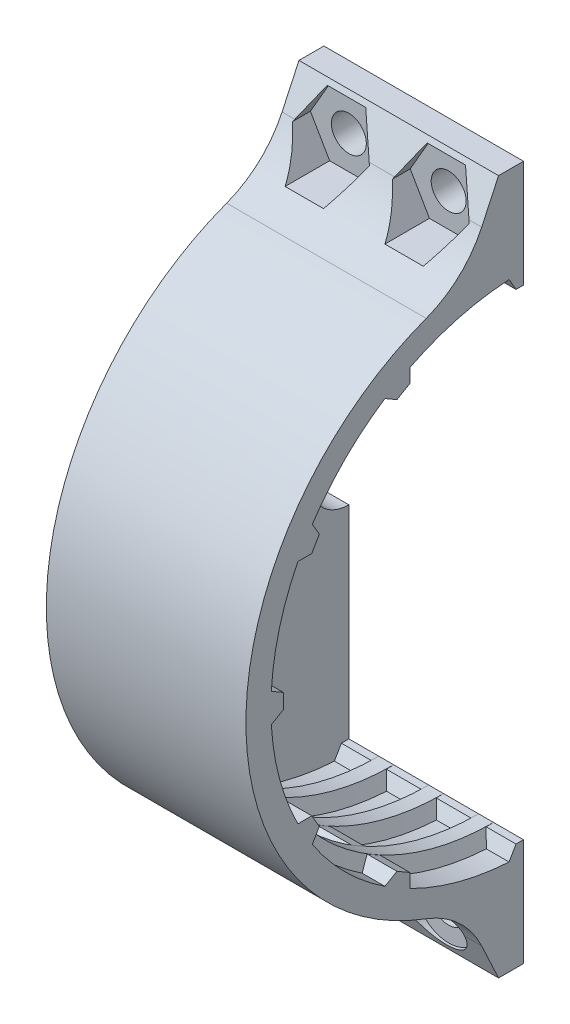
SolidWorks part; units mm, degrees
ref_plane "Front Plane" through (0, 0, 0) normal (0, 0, 1) x (1, 0, 0)
ref_plane "Top Plane" through (0, 0, 0) normal (0, 1, 0) x (1, 0, 0)
ref_plane "Right Plane" through (0, 0, 0) normal (1, 0, 0) x (0, 0, -1)
sketch "Sketch1" plane through (0, 0, 0) normal (0, 1, 0) x (1, 0, 0)
  line L0 (0, 4.7625) -> (0, 35.3219)
  line L1 (0, 35.3219) -> (25.4, 35.3219)
  line L2 (25.4, 35.3219) -> (25.4, 32.1469)
  line L3 (25.4, 32.1469) -> (3.175, 32.1469)
  line L4 (3.175, 32.1469) -> (3.175, 4.7625)
  line L8 (1.5875, 0) -> (24.5079, 0) construction
  line L9 (0, 4.7625) -> (3.175, 4.7625)
  line L15 (13.335, 30.5594) -> (15.24, 30.5594)
  line L16 (15.24, 30.5594) -> (16.1565, 32.1469)
  line L17 (6.985, 30.5594) -> (6.0685, 32.1469)
  line L18 (6.985, 33.7344) -> (8.89, 33.7344)
  line L19 (6.985, 33.7344) -> (6.985, 30.5594)
  line L20 (6.985, 30.5594) -> (8.89, 30.5594)
  line L21 (8.89, 33.7344) -> (8.89, 30.5594)
  line L22 (6.985, 33.7344) -> (8.89, 30.5594) construction
  line L23 (6.985, 30.5594) -> (8.89, 33.7344) construction
  line L28 (13.335, 33.7344) -> (15.24, 30.5594) construction
  line L29 (13.335, 30.5594) -> (12.4185, 32.1469)
  line L30 (8.89, 30.5594) -> (9.8065, 32.1469)
  line L31 (13.335, 33.7344) -> (13.335, 30.5594)
  line L32 (13.335, 30.5594) -> (15.24, 33.7344) construction
  line L33 (13.335, 33.7344) -> (15.24, 33.7344)
  line L34 (15.24, 33.7344) -> (15.24, 30.5594)
  line L35 (19.685, 30.5594) -> (21.59, 30.5594)
  line L36 (21.59, 30.5594) -> (22.5065, 32.1469)
  line L37 (19.685, 33.7344) -> (21.59, 30.5594) construction
  line L38 (19.685, 30.5594) -> (18.7685, 32.1469)
  line L39 (19.685, 33.7344) -> (19.685, 30.5594)
  line L40 (19.685, 30.5594) -> (21.59, 33.7344) construction
  line L41 (19.685, 33.7344) -> (21.59, 33.7344)
  line L42 (21.59, 33.7344) -> (21.59, 30.5594)
  line L43 (6.985, 30.5594) -> (13.335, 30.5594) construction
  point P13 (7.9375, 32.1469)
  dimension "D8" = 4.7625
  dimension "D2" = 64.2938
  dimension "D3" = 3.175
  dimension "D4" = 3.175
  dimension "D5" = 30
  dimension "D6" = 9.525
  dimension "D7" = 1.905
  dimension "D9" = 3.175
  dimension "D10" = 6.35
  dimension "D11" = 3
  dimension "D12" = 22.225
revolve "Revolve1" add sketch "Sketch1" angle 360 about L8 region at (0.3974, 0, -20.0422) region at (6.6795, 0, -31.6177) region at (21.8955, 0, -31.6177) region at (7.9375, 0, -32.9406) region at (7.9375, 0, -31.3531) region at (20.6375, 0, -31.3531) region at (20.6375, 0, -32.9406) region at (9.1955, 0, -31.6177) region at (19.3795, 0, -31.6177) region at (13.0295, 0, -31.6177) region at (15.5455, 0, -31.6177) region at (14.2875, 0, -32.9406) region at (14.2875, 0, -31.3531)
sketch "Sketch2" plane through (3.175, 0, 0) normal (1, 0, 0) x (0, 0, -1)
  line L0 (0, 32.1469) -> (0, 30.5594) construction
  line L1 (-0.9525, 30.5594) -> (0.9525, 30.5594)
  line L2 (-0.9525, 30.5594) -> (-1.8387, 32.0943)
  line L3 (0.9525, 30.5594) -> (1.8387, 32.0943)
  line L4 (-0.9525, 30.5594) -> (-0.9525, 32.1328) construction
  line L5 (0.9525, 30.5594) -> (0.9525, 32.1328) construction
  circle A0 centre (0, 0) radius 32.1469 construction
  arc A6 (-1.8387, 32.0943) -> (1.8387, 32.0943) centre (0, 0) cw
  circle A7 centre (0, 0) radius 30.5594 construction
  point P12 (0, 30.5594)
  dimension "D1" = 1.905
  dimension "D2" = 30
  dimension "D3" = 30
extrude "Boss-Extrude1" add sketch "Sketch2" along normal up to surface (22.225 mm away) up to face at (25.4, 0, 32.1469)
pattern_circular "CirPattern1" count 12 every 30 about axis through (1.5875, 0, 0) along (-1, 0, 0) of "Boss-Extrude1"
sketch "Sketch4" plane through (25.4, 0, 0) normal (1, 0, 0) x (0, 0, -1)
  line L0 (0, 35.3219) -> (0, 44.2119) construction
  line L5 (3.175, 44.2119) -> (-3.175, 44.2119)
  line L6 (-3.175, 44.2119) -> (-7.7185, 34.4682)
  line L7 (-3.175, 44.2119) -> (-3.175, 35.1789) construction
  line L8 (3.175, 44.2119) -> (3.175, 35.1789) construction
  line L9 (3.175, 44.2119) -> (7.7185, 34.4682)
  circle A1 centre (0, 0) radius 35.3219 construction
  arc A2 (-7.7185, 34.4682) -> (7.7185, 34.4682) centre (0, 0) cw
  point P13 (0, 0)
  point P14 (2.54, 42.658)
  point P15 (0, 0)
  point P16 (0, 35.3219)
  dimension "D1" = 8.89
  dimension "D2" = 3.175
  dimension "D3" = 25
extrude "Boss-Extrude2" add sketch "Sketch4" against normal up to surface (25.4 mm away) up to face at (0, 0, 35.3219)
sketch "Sketch5" plane through (0, 0, 0) normal (0, 0, 1) x (1, 0, 0)
  line L0 (0, 44.2119) -> (0, 34.4682) construction
  line L1 (25.4, 44.2119) -> (25.4, 34.4682) construction
  circle A0 centre (6.35, 39.3401) radius 2.2225
  circle A1 centre (19.05, 39.3401) radius 2.2225
  point P6 (0, 39.3401)
  point P7 (0, 0)
  point P10 (0, 0)
  dimension "D1" = 4.445
  dimension "D2" = 6.35
  dimension "D3" = 6.35
extrude "Cut-Extrude2" cut sketch "Sketch5" against normal through all both and the other way through all
ref_plane "Plane1" through (0, 0, 7.62) normal (0, 0, 1) x (1, 0, 0)
sketch "Sketch6" plane through (0, 0, 7.62) normal (0, 0, 1) x (1, 0, 0)
  line L1 (11.2395, 39.3401) -> (8.7947, 43.5745)
  line L2 (8.7947, 43.5745) -> (3.9052, 43.5745)
  line L3 (3.9052, 43.5745) -> (1.4605, 39.3401)
  line L4 (1.4605, 39.3401) -> (3.9052, 35.1056)
  line L5 (3.9052, 35.1056) -> (8.7947, 35.1056)
  line L6 (8.7947, 35.1056) -> (11.2395, 39.3401)
  line L7 (23.9395, 39.3401) -> (21.4947, 43.5745)
  line L8 (21.4947, 43.5745) -> (16.6052, 43.5745)
  line L9 (16.6052, 43.5745) -> (14.1605, 39.3401)
  line L10 (14.1605, 39.3401) -> (16.6052, 35.1056)
  line L11 (16.6052, 35.1056) -> (21.4947, 35.1056)
  line L12 (21.4947, 35.1056) -> (23.9395, 39.3401)
  circle A1 centre (6.35, 39.3401) radius 4.2344 construction
  circle A2 centre (19.05, 39.3401) radius 4.2344 construction
  point P1 (0, 0)
  dimension "D1" = 4.8895
extrude "Cut-Extrude4" cut sketch "Sketch6" against normal up to vertex (4.445 mm away) up to point (25.4, 44.2119, 3.175)
fillet "Fillet1" radius 12.7 2 edges at (12.7, 34.4682, 7.7185) (12.7, 34.4682, -7.7185)
mirror "Mirror2" about plane through (0, 0, 0) normal (0, 1, 0) of "Boss-Extrude2", "Cut-Extrude2", "Fillet1"
sketch "Sketch7" plane through (0, 0, 7.62) normal (0, 0, 1) x (1, 0, 0)
  circle A0 centre (19.05, -39.3401) radius 4.191
  circle A1 centre (6.35, -39.3401) radius 4.191
  dimension "D1" = 8.382
extrude "Cut-Extrude5" cut sketch "Sketch7" against normal up to vertex (4.445 mm away) and the other way blind 4.572 up to point (25.4, -44.2119, 3.175)
sketch "Sketch3" plane through (3.175, 0, 0) normal (1, 0, 0) x (0, 0, -1)
  line L0 (38.1, 50.8) -> (38.1, -50.8)
  line L2 (0, 0) -> (0, 50.8)
  line L3 (0, 50.8) -> (38.1, 50.8)
  line L6 (0, 0) -> (0, -50.8)
  line L7 (0, -50.8) -> (38.1, -50.8)
  point P3 (0, 0)
  point P13 (38.1, 0)
  dimension "D1" = 101.6
  dimension "D2" = 38.1
extrude "Cut-Extrude1" cut sketch "Sketch3" against normal through all both and the other way through all
